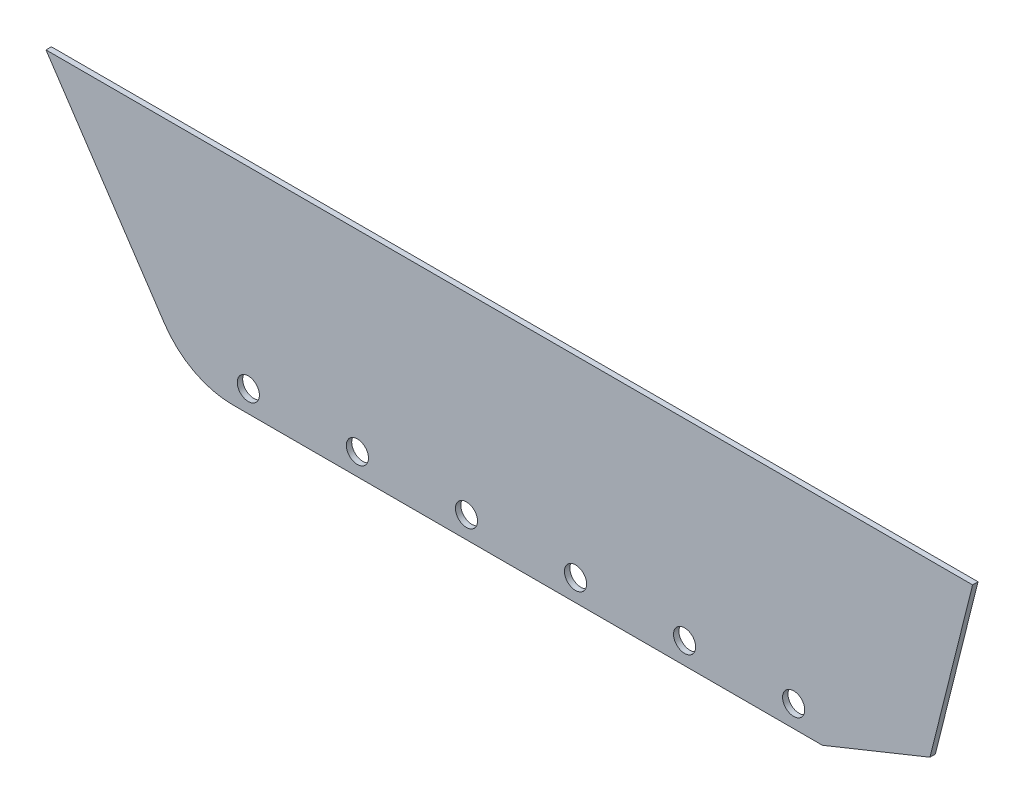
SolidWorks part; units mm, degrees
material "5052-H34"
ref_plane "Front Plane" through (0, 0, 0) normal (0, 0, 1) x (1, 0, 0)
ref_plane "Top Plane" through (0, 0, 0) normal (0, 1, 0) x (1, 0, 0)
ref_plane "Right Plane" through (0, 0, 0) normal (1, 0, 0) x (0, 0, -1)
sketch "Sketch1" plane through (0, 0, 0) normal (0, 0, 1) x (1, 0, 0)
  line L6 (-98.8794, 3.851) -> (-31.8794, -96.649)
  line L7 (428.1206, 28.9396) -> (403.1206, -71.149)
  line L9 (403.1206, -71.149) -> (366, -96.649)
  line L10 (-31.8794, -96.649) -> (366, -96.649)
  line L12 (-98.8794, 3.851) -> (-115.6052, 28.9396)
  line L13 (-115.6052, 28.9396) -> (428.1206, 28.9396)
  circle A0 centre (3.1206, -83.899) radius 6.5
  circle A1 centre (67.1206, -83.899) radius 6.5
  circle A2 centre (131.1206, -83.899) radius 6.5
  circle A3 centre (195.1206, -83.899) radius 6.5
  circle A4 centre (259.1206, -83.899) radius 6.5
  circle A5 centre (323.1206, -83.899) radius 6.5
  point P0 (-48.8794, -71.149)
  point P2 (-31.8794, -96.649)
  point P8 (48, -83.899)
  point P9 (403.1206, -71.149)
  dimension "D2" = 64
  dimension "D4" = 64
  dimension "D14" = 13
  dimension "D1" = 25.5
  dimension "D3" = 75
  dimension "D5" = 25
  dimension "D6" = 80
  dimension "D7" = 527
  dimension "D8" = 180
  dimension "D9" = 64
  dimension "D10" = 64
  dimension "D11" = 64
  dimension "D12" = 123.69
  dimension "D13" = 12.75
  dimension "D15" = 366
  dimension "D16" = 115.6052
extrude "Boss-Extrude1" add sketch "Sketch1" along normal blind 3.175 contours L12 L13 L7 L9 L10 L6
extrude "Cut-Extrude1" cut sketch "Sketch1<4>" along normal through all contours A0 | A1 | A2 | A3 | A4 | A5 region at (3.1206, -83.899, 0)
sketch "Sketch1<4>" plane through (0, 0, 0) normal (0, 0, 1) x (1, 0, 0) same geometry as "Sketch1"
sketch "Sketch2" plane through (0, 0, 0) normal (0, 0, -1) x (-1, 0, 0)
  circle A0 centre (-291.1206, -83.899) radius 6.5
  circle A2 centre (-241.5603, -124.3932) radius 6.5
  circle A3 centre (-192, -83.899) radius 6.5
  circle A4 centre (-128, -83.899) radius 6.5
  circle A5 centre (-64, -83.899) radius 6.5
  circle A6 centre (0, -83.899) radius 6.5
  dimension "D2" = 0
  dimension "D3" = 64
  dimension "D4" = 64
  dimension "D5" = 64
  dimension "D6" = 64
  dimension "D7" = 64
  dimension "D1" = 32
sketch "Sketch5" plane through (0, 0, 0) normal (0, 0, -1) x (-1, 0, 0)
  line L0 (48.8794, -71.149) -> (-14.2353, -96.649)
  line L1 (31.8794, -96.649) -> (-366, -96.649) construction
  line L2 (-14.2353, -96.649) -> (31.8794, -96.649)
  line L3 (31.8794, -96.649) -> (48.8794, -71.149)
  line L6 (-366, -96.649) -> (-403.1206, -71.149)
  line L7 (-403.1206, -71.149) -> (-352, -71.149)
  line L9 (-352, -71.149) -> (-326.5, -96.649)
  line L11 (-366, -96.649) -> (-326.5, -96.649)
  dimension "D1" = 22
  dimension "D2" = 45
extrude "Cut-Extrude2" [suppressed] cut sketch "Sketch5" against normal up to next
sketch "Sketch6" plane through (0, 0, 3.175) normal (0, 0, 1) x (1, 0, 0)
  line L0 (-48.8794, -71.149) -> (14.2353, -96.649)
  line L1 (-31.8794, -96.649) -> (366, -96.649) construction
  line L2 (14.2353, -96.649) -> (-31.8794, -96.649)
  line L3 (-31.8794, -96.649) -> (-48.8794, -71.149)
  dimension "D1" = 158
fillet "Fillet1" radius 48 1 edges at (-31.8794, -96.649, 1.5875)
sketch "Sketch7" plane through (0, 0, 3.175) normal (0, 0, 1) x (1, 0, 0)
  line L0 (403.1206, -71.149) -> (340.0059, -96.649)
  line L1 (-31.8794, -96.649) -> (366, -96.649) construction
  line L2 (340.0059, -96.649) -> (366, -96.649)
  line L3 (366, -96.649) -> (403.1206, -71.149)
  dimension "D1" = 22
extrude "Cut-Extrude3" cut sketch "Sketch7" against normal blind 10
sketch "Sketch9" plane through (0, 0, 0) normal (0, 0, -1) x (-1, 0, 0)
  line L0 (-403.1206, -71.149) -> (48.8794, -71.149)
  line L1 (48.8794, -71.149) -> (48.8794, -114.9143)
  line L2 (48.8794, -114.9143) -> (-403.1206, -114.9143)
  line L3 (-403.1206, -114.9143) -> (-403.1206, -71.149)
extrude "Cut-Extrude4" [suppressed] cut sketch "Sketch9" against normal blind 10
sketch "Sketch10" plane through (0, 0, 0) normal (0, 0, -1) x (-1, 0, 0)
  circle A0 centre (-396.933, -27.611) radius 6.5
  dimension "D1" = 13
